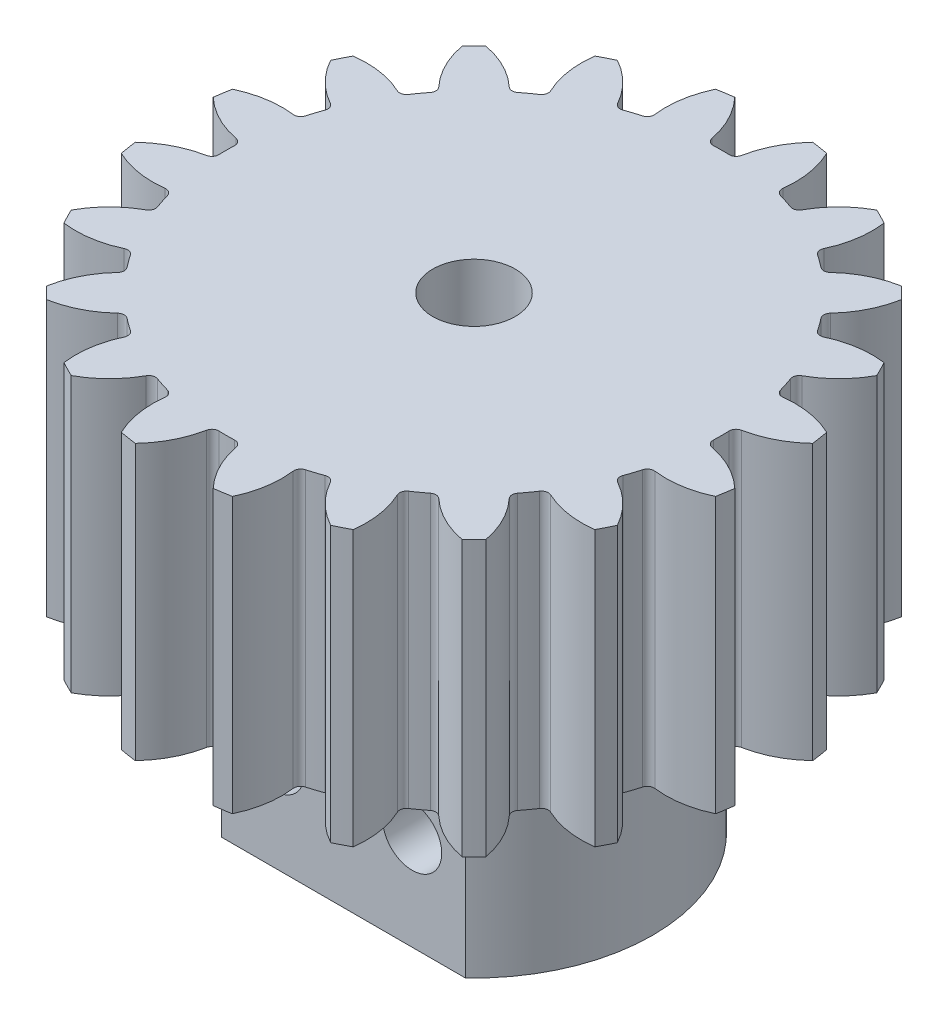
SolidWorks part; units mm, degrees
ref_plane "前视基准面" through (0, 0, 0) normal (0, 0, 1) x (1, 0, 0)
ref_plane "上视基准面" through (0, 0, 0) normal (0, 1, 0) x (1, 0, 0)
ref_plane "右视基准面" through (0, 0, 0) normal (1, 0, 0) x (0, 0, -1)
other "Configuration Table"
sketch "草图1" plane through (0, 0, 0) normal (0, 1, 0) x (1, 0, 0)
  circle A0 centre (0, 0) radius 22
  dimension "D1" = 44
extrude "凸台-拉伸1" add sketch "草图1" along normal blind 20
sketch "草图2" plane through (0, 0, 0) normal (0, 1, 0) x (1, 0, 0)
  line L0 (0, 31.928) -> (0, -25.5383) construction
  line L1 (0, 0) -> (2.536, 32.2233) construction
  line L2 (1.5692, 19.9383) -> (22.0342, 18.3277) construction
  line L3 (1.5692, 19.9383) -> (21.6093, 10.8055) construction
  line L4 (0, 0) -> (7.7937, 17.1017) construction
  circle A0 centre (0, 0) radius 20 construction
  circle A1 centre (0, 0) radius 22 construction
  arc A2 (2.8375, 21.8162) -> (-2.8375, 21.8162) centre (0, 0) ccw
  arc A3 (2.8375, 21.8162) -> (1.0769, 18.3961) centre (7.7937, 17.1017) ccw
  arc A4 (0.5701, 17.991) -> (-0.5701, 17.991) centre (0, 0) ccw
  arc A5 (1.0769, 18.3961) -> (0.5701, 17.991) centre (0.5859, 18.4907) cw
  arc A6 (-1.0769, 18.3961) -> (-0.5701, 17.991) centre (-0.5859, 18.4907) ccw
  arc A7 (-2.8375, 21.8162) -> (-1.0769, 18.3961) centre (-7.7937, 17.1017) cw
  dimension "D2" = 40
  dimension "D4" = 18
  dimension "D5" = 0.5
  dimension "D1" = 4.5
  dimension "D3" = 20
extrude "切除-拉伸1" cut sketch "草图2" along normal through all
pattern_circular "阵列(圆周)1" count 20 over 360 about axis through (0, 20, 0) along (0, 1, 0) of "切除-拉伸1"
sketch "草图3" plane through (0, 0, 0) normal (0, 1, 0) x (1, 0, 0)
  circle A0 centre (0, 0) radius 13
  dimension "D1" = 26
extrude "凸台-拉伸2" add sketch "草图3" against normal blind 14
sketch "草图4" plane through (0, 0, 0) normal (0, 0, 1) x (1, 0, 0)
  line L0 (-13, -14) -> (13, -14) construction
  line L1 (-13, -14) -> (13, -14)
  line L2 (-13, -14) -> (-13, 0)
  line L3 (-13, 0) -> (13, 0)
  line L4 (13, -14) -> (13, 0)
extrude "切除-拉伸2" cut sketch "草图4" against normal blind 3.5 from offset 13
extrude "切除-拉伸3" cut sketch "草图4<2>" along normal blind 3.5 from offset 13 offset against normal yes
sketch "草图4<2>" plane through (0, 0, 0) normal (0, 0, 1) x (1, 0, 0) same geometry as "草图4"
sketch "草图5" plane through (0, 0, 0) normal (0, 0, 1) x (1, 0, 0)
  line L0 (0, 25.2097) -> (0, -18.3557) construction
  circle A0 centre (5, -7) radius 2.15
  circle A1 centre (-5, -7) radius 2.15
  dimension "D1" = 4.3
  dimension "D2" = 10
  dimension "D3" = 7
extrude "切除-拉伸4" cut sketch "草图5" against normal through all both and the other way through all
sketch "草图6" plane through (0, 0, 0) normal (0, 1, 0) x (1, 0, 0)
  circle A0 centre (0, 0) radius 3
  dimension "D1" = 6
extrude "切除-拉伸5" cut sketch "草图6" against normal through all both and the other way through all
